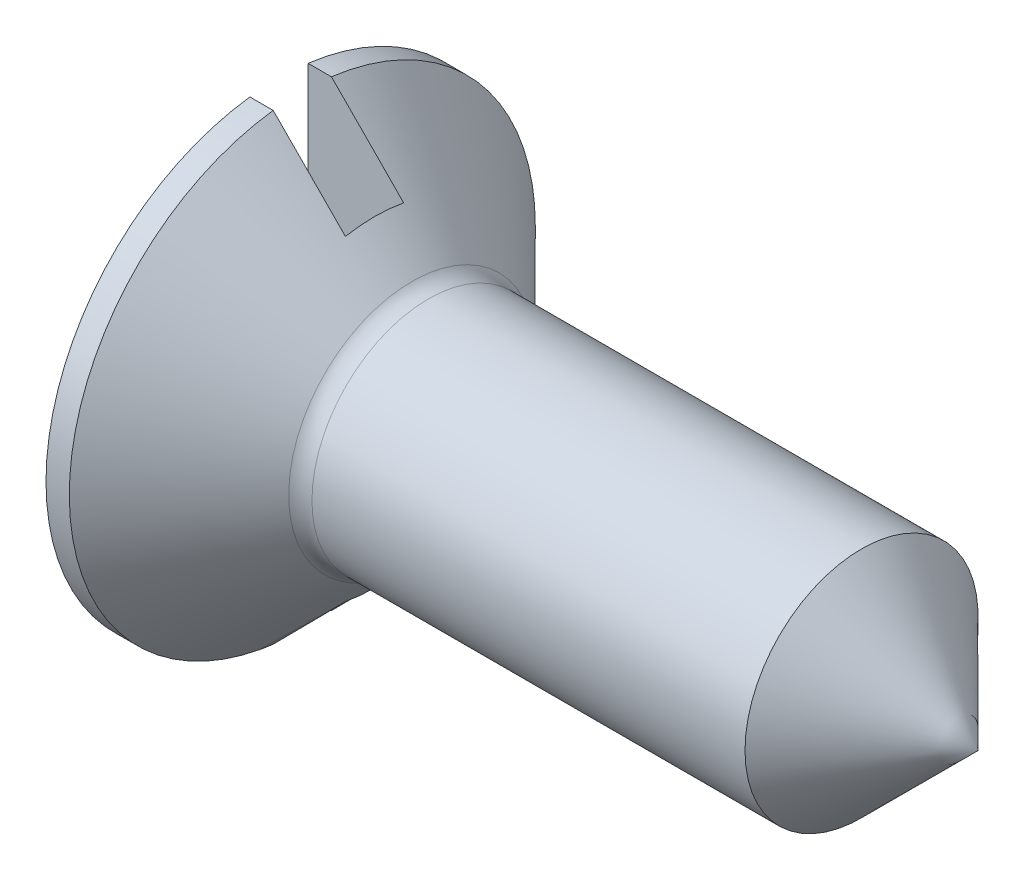
SolidWorks part; units mm, degrees
ref_plane "Front" through (0, 0, 0) normal (0, 0, 1) x (1, 0, 0)
ref_plane "Top" through (0, 0, 0) normal (0, 1, 0) x (1, 0, 0)
ref_plane "Right" through (0, 0, 0) normal (1, 0, 0) x (0, 0, -1)
sketch "Sketch2" plane through (1.6093, 0, 0.5907) normal (0, 1, 0) x (0, 0, -1)
  line L0 (0.5907, -4.3907) -> (0.5907, 1.3247) construction
  line L3 (1.5907, 0.4093) -> (2.7907, 1.6093)
  line L5 (0.5907, 0.4093) -> (1.5907, 0.4093)
  line L6 (2.7907, 1.6093) -> (0.5907, 1.6093)
  line L7 (0.5907, 1.6093) -> (0.5907, 0.4093)
  dimension "D2" = 45
revolve "BaseHead" add sketch "Sketch2" angle 360 about L0
sketch "Sketch1" plane through (1.2, -0.0348, 0.0561) normal (1, 0, 0) x (0, 0, -1)
  circle A0 centre (0.0561, 0.0348) radius 1
extrude "BaseBody" add sketch "Sketch1" along normal blind 4.8
cosmetic thread "ThreadCosmetic1" [suppressed] parameters "D1"=3, "D2"=1.5
sketch "Sketch3" plane through (0, -1.059, 0.7678) normal (-1, 0, 0) x (0, 0, 1)
  circle A0 centre (-0.7678, 1.059) radius 2
  circle A1 centre (-0.7678, 1.059) radius 2.2 construction
  circle A3 centre (-0.7678, 1.059) radius 2.2
  dimension "dk" = 4
extrude "Cut-Extrude1" cut sketch "Sketch3" against normal through all
sketch "Sketch4" plane through (1.4152, 0, -1.4152) normal (0, 1, 0) x (0, 0, -1)
  line L0 (-1.4152, 0.4723) -> (-1.4152, 2.4503) construction
  line L1 (-1.1652, 0.5952) -> (-1.6652, 0.5952)
  line L2 (-1.1652, 0.5952) -> (-1.1652, 1.4152)
  line L3 (-1.1652, 1.4152) -> (-1.6652, 1.4152)
  line L4 (-1.6652, 0.5952) -> (-1.6652, 1.4152)
  line L7 (0.5848, 1.4152) -> (-3.4152, 1.4152) construction
  dimension "n" = 0.5
  dimension "t" = 0.82
extrude "Slot" cut sketch "Sketch4" against normal through all and the other way through all
sketch "Sketch5" plane through (23.6694, -6.3306, 0) normal (0, 0, 1) x (0, 1, 0)
  line L0 (6.3306, -6.6611) -> (6.3306, -3.7572) construction
  line L2 (6.3306, 17.324) -> (36.3306, 17.324)
  line L3 (36.3306, 17.324) -> (36.3306, 47.6694)
  line L4 (36.3306, 47.6694) -> (6.3306, 17.6694)
  line L5 (6.3306, 17.6694) -> (6.3306, 17.324)
  line L7 (5.3306, 17.6694) -> (7.3306, 17.6694) construction
  dimension "D1" = 45
  dimension "D2" = 30
  dimension "D3" = 0.3455
revolve "Cut-Revolve1" cut sketch "Sketch5" angle 360 about L0
fillet "Fillet1" radius 0.2 1 edges at (1.2, 0, -1)
sketch "Sketch6" [suppressed] plane through (0, 0, 0) normal (0, 0, 1) x (1, 0, 0)
  line L0 (3.2, 1.2) -> (3.45, 1.2)
  line L1 (3.45, 1.2) -> (3.45, 1)
  line L2 (3.45, 1) -> (3.325, 0.7835)
  line L3 (3.2, 1) -> (3.325, 0.7835)
  line L4 (3.2, 1.2) -> (3.2, 1)
  line L5 (10.7743, 0) -> (0, 0) construction
  line L6 (3.2, 1) -> (3.45, 1) construction
  line L7 (3.325, 1) -> (3.325, 0.7835) construction
  line L8 (6.2, 1) -> (1.2828, 1) construction
  point P5 (3.325, 1.2)
  dimension "D1" = 0.2
  dimension "D2" = 0.25
  dimension "D3" = 4
revolve "Cut-Revolve10" [suppressed] cut sketch "Sketch6" angle 360 about L5
pattern_linear "LPattern10" [suppressed] count 8 spacing 0.5 of bodies 106
equation "\"D1@Sketch2\" = \"d@Sketch1\" / 2"
equation "\"D3@Sketch6\" = \"D1@ThreadCosmetic1\" + \"d@Sketch1\" / 2"
equation "\"D2@Sketch6\" = (  \"d@Sketch1\" - \"D2@ThreadCosmetic1\" )  / 2"
equation "\"D3@LPattern10\" = \"D2@Sketch6\" * 2"
equation "\"D1@LPattern10\" = \"D3@Sketch6\" / \"D3@LPattern10\""
equation "\"l@BaseBody\" = \"l@Sketch2\" - \"k@Sketch2\""
